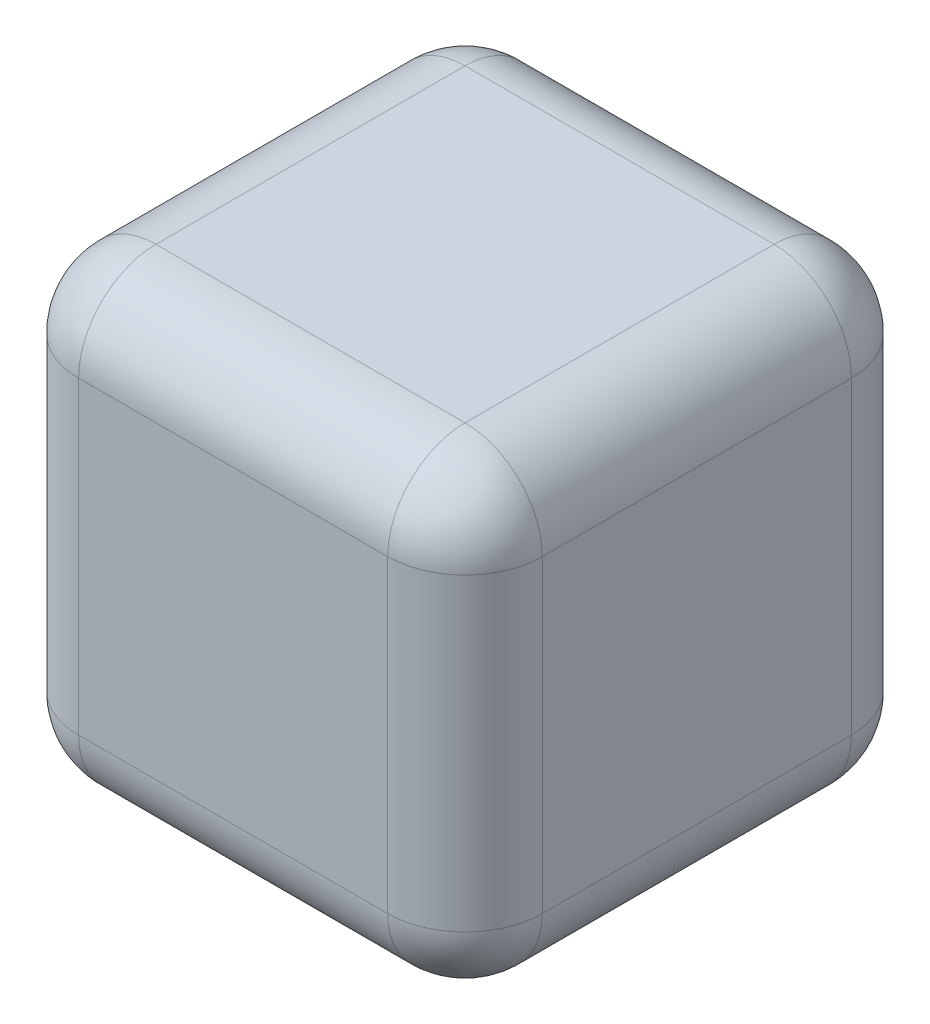
SolidWorks part; units mm, degrees
ref_plane "Front Plane" through (0, 0, 0) normal (0, 0, 1) x (1, 0, 0)
ref_plane "Top Plane" through (0, 0, 0) normal (0, 1, 0) x (1, 0, 0)
ref_plane "Right Plane" through (0, 0, 0) normal (1, 0, 0) x (0, 0, -1)
sketch "Sketch2" plane through (0, 0, 0) normal (0, 1, 0) x (1, 0, 0)
  line L1 (-300, -300) -> (300, -300)
  line L2 (-300, -300) -> (-300, 300)
  line L3 (-300, 300) -> (300, 300)
  line L4 (300, -300) -> (300, 300)
  point P7 (-20.9751, 66.0682)
  dimension "D1" = 600
  dimension "D2" = 600
  dimension "D3" = 300
  dimension "D4" = 300
extrude "Boss-Extrude1" add sketch "Sketch2" along normal blind 300 and the other way blind 300
fillet "Fillet4" radius 100 12 edges at (300, 300, 0) (0, 300, 300) (300, 0, 300) (0, -300, 300) (300, -300, 0) (-300, -300, 0) (-300, 300, 0) (-300, 0, 300) (0, -300, -300) (300, 0, -300) (0, 300, -300) (-300, 0, -300)
